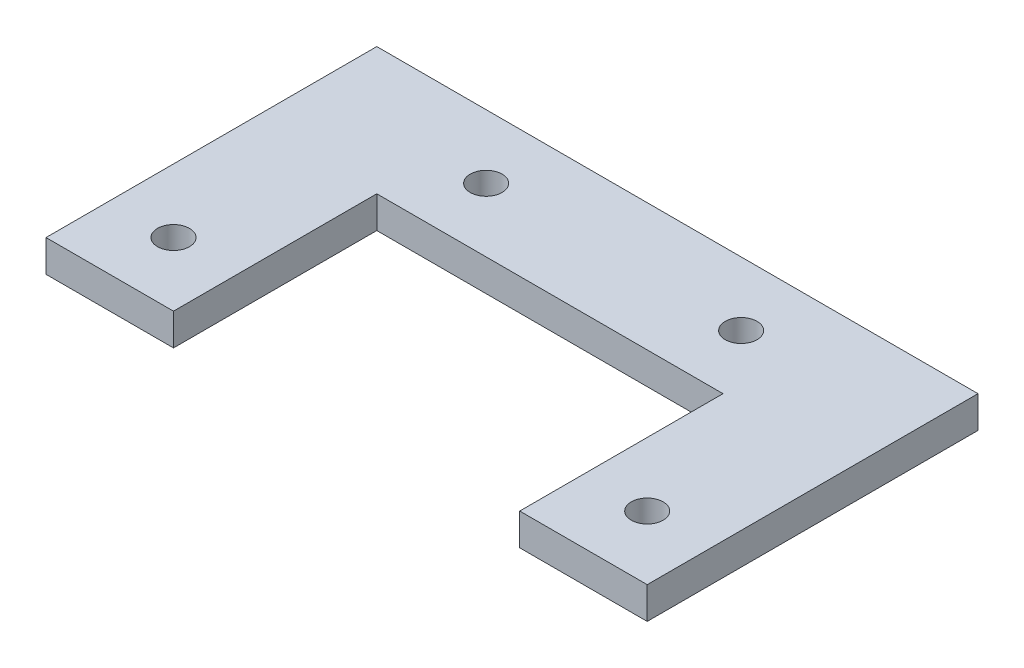
SolidWorks part; units mm, degrees
material "1060 Alloy"
ref_plane "Front Plane" through (0, 0, 0) normal (0, 0, 1) x (1, 0, 0)
ref_plane "Top Plane" through (0, 0, 0) normal (0, 1, 0) x (1, 0, 0)
ref_plane "Right Plane" through (0, 0, 0) normal (1, 0, 0) x (0, 0, -1)
sketch "Sketch1" plane through (0, 0, 0) normal (0, 1, 0) x (1, 0, 0)
  line L0 (-23.5938, -13.9008) -> (-17.2438, -13.9008) construction
  line L1 (0, 0) -> (0, 12.7) construction
  line L2 (-23.5938, -13.9008) -> (-23.5938, -20.2508) construction
  line L3 (29.9438, 12.7) -> (-29.9438, 12.7)
  line L4 (-29.9438, 12.7) -> (-29.9438, -20.2508)
  line L5 (-29.9438, -20.2508) -> (-17.2438, -20.2508)
  line L6 (0, 6.35) -> (-29.9438, 6.35) construction
  line L8 (-17.2438, -20.2508) -> (-17.2438, 0)
  line L9 (-17.2438, 0) -> (17.2438, 0)
  line L10 (29.9438, 12.7) -> (29.9438, -20.2508)
  line L11 (29.9438, -20.2508) -> (17.2438, -20.2508)
  line L12 (17.2438, -20.2508) -> (17.2438, 0)
  line L18 (38.1, 12.7) -> (-38.1, 12.7) construction
  line L20 (-23.5938, -13.9008) -> (-23.5938, 12.7) construction
  circle A0 centre (-23.5938, -13.9008) radius 1.5875
  circle A2 centre (23.5938, -13.9008) radius 1.5875
  circle A3 centre (-12.7, 6.35) radius 1.5875
  circle A4 centre (12.7, 6.35) radius 1.5875
  point P5 (-23.5938, -13.9008)
  dimension "D2" = 3.175
  dimension "D4" = 3.175
  dimension "D1" = 6.35
  dimension "D3" = 12.7
extrude "Boss-Extrude1" add sketch "Sketch1" along normal blind 3.175
